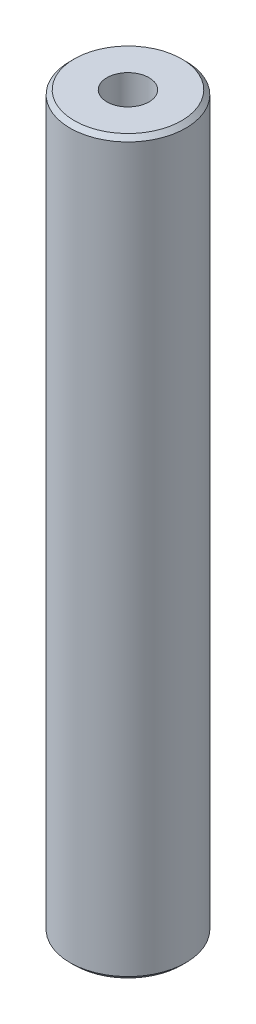
SolidWorks part; units mm, degrees
ref_plane "Front Plane" through (0, 0, 0) normal (0, 0, 1) x (1, 0, 0)
ref_plane "Top Plane" through (0, 0, 0) normal (0, 1, 0) x (1, 0, 0)
ref_plane "Right Plane" through (0, 0, 0) normal (1, 0, 0) x (0, 0, -1)
sketch "Sketch1" plane through (0, 0, 0) normal (0, 1, 0) x (1, 0, 0)
  circle A0 centre (0, 0) radius 47.5
  dimension "SHAFT_OD" = 95
extrude "Boss-Extrude1" add sketch "Sketch1" along normal blind 600
sketch "Sketch2" plane through (0, 0, 0) normal (0, 1, 0) x (1, 0, 0)
  circle A0 centre (0, 0) radius 17.2621
  dimension "BORE_D" = 34.5242
extrude "Cut-Extrude1" cut sketch "Sketch2" along normal through all
chamfer "Chamfer1" distance 3.512 angle 45 2 edges at (0, 600, 47.5) (0, 0, 47.5)
